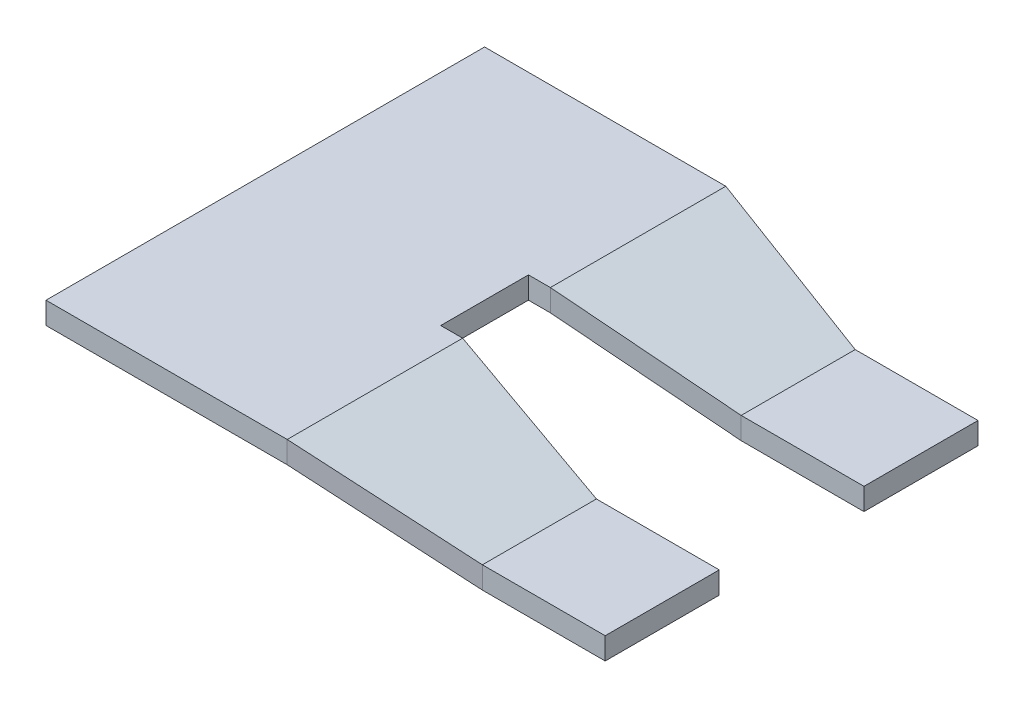
SolidWorks part; units mm, degrees
ref_plane "前视基准面" through (0, 0, 0) normal (0, 0, 1) x (1, 0, 0)
ref_plane "上视基准面" through (0, 0, 0) normal (0, 1, 0) x (1, 0, 0)
ref_plane "右视基准面" through (0, 0, 0) normal (1, 0, 0) x (0, 0, -1)
other "Configuration Table"
sketch "草图1" plane through (0, 0, 0) normal (0, 1, 0) x (1, 0, 0)
  line L1 (0, -50) -> (50, -50)
  line L2 (0, -50) -> (0, 50)
  line L3 (0, 50) -> (50, 50)
  line L4 (50, -50) -> (50, 50)
  line L11 (92, 42.5) -> (120, 42.5)
  line L12 (92, 42.5) -> (92, -42.5)
  line L13 (92, -42.5) -> (120, -42.5)
  line L14 (120, 42.5) -> (120, -42.5)
  line L15 (92, 16.5) -> (120, 16.5)
  line L16 (92, 16.5) -> (92, -16.5)
  line L17 (92, -16.5) -> (120, -16.5)
  line L18 (120, 16.5) -> (120, -16.5)
  point P0 (0, 0)
  point P2 (0, 0)
  point P11 (92, 0)
  point P16 (92, 0)
  dimension "D1" = 50
  dimension "D2" = 100
  dimension "D3" = 33
  dimension "D4" = 85
  dimension "D5" = 28
  dimension "D6" = 120
extrude "凸台-拉伸1" add sketch "草图1" along normal blind 5 contours L12 L15 L14 L11 | L17 L12 L13 L14 region at (106, 0, -29.5) region at (106, 0, 29.5)
extrude "凸台-拉伸2" add sketch "草图1<12>" along normal blind 5 from offset 10 separate body contours L3 L4 L1 L2
sketch "草图1<12>" plane through (0, 0, 0) normal (0, 1, 0) x (1, 0, 0) same geometry as "草图1"
sketch "草图2" plane through (50, 0, 0) normal (1, 0, 0) x (0, 0, -1)
  line L0 (50, 15) -> (50, 10) construction
  line L1 (50, 15) -> (10, 15)
  line L2 (50, 15) -> (50, 10)
  line L3 (50, 10) -> (10, 10)
  line L4 (10, 15) -> (10, 10)
  line L5 (-50, 15) -> (50, 15) construction
  line L6 (-50, 10) -> (50, 10) construction
  line L7 (-50, 15) -> (-50, 10) construction
  line L8 (-50, 15) -> (-10, 15)
  line L9 (-50, 15) -> (-50, 10)
  line L10 (-50, 10) -> (-10, 10)
  line L11 (-10, 15) -> (-10, 10)
  dimension "D1" = 40
extrude "凸台-拉伸3" add sketch "草图2" along normal blind 5
loft "放样5" add section face at (55, 12.5, 30) section face at (92, 2.5, 29.5) connector at (55, 15, 50) connector at (92, 5, 42.5)
loft "放样6" add section face at (55, 12.5, -30) section face at (92, 2.5, -29.5) connector at (55, 15, -10) connector at (92, 5, -16.5)
